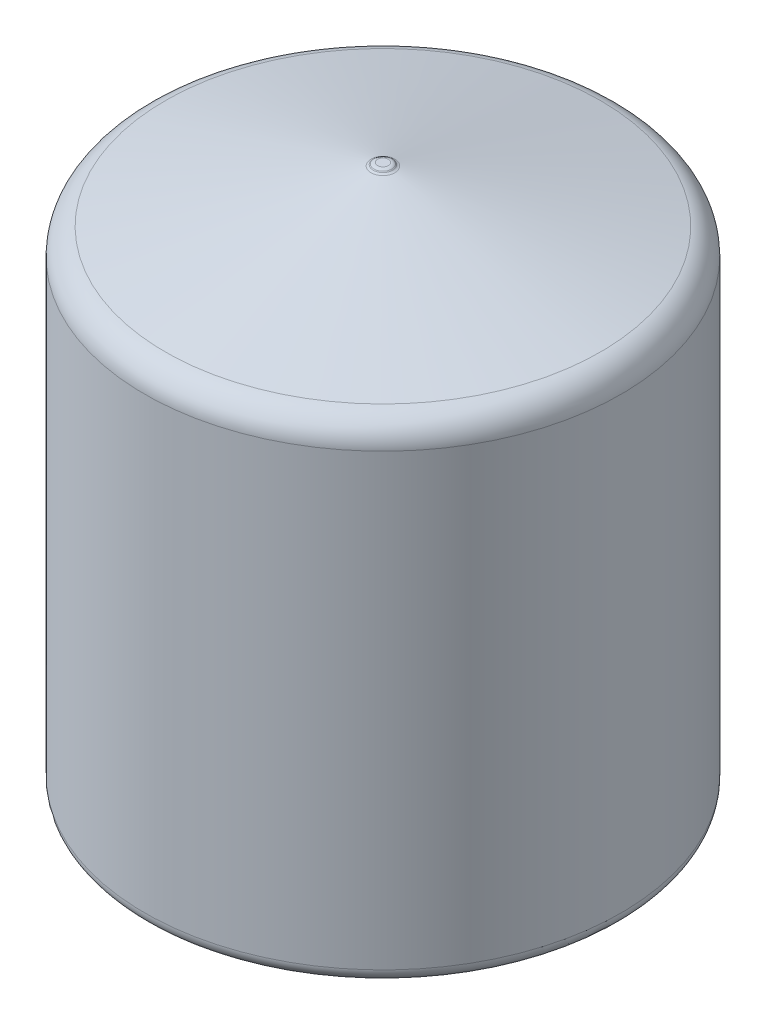
SolidWorks part; units mm, degrees
material "Zinc AC41A Alloy, As Cast"
ref_plane "Front Plane" through (0, 0, 0) normal (0, 0, 1) x (1, 0, 0)
ref_plane "Top Plane" through (0, 0, 0) normal (0, 1, 0) x (1, 0, 0)
ref_plane "Right Plane" through (0, 0, 0) normal (1, 0, 0) x (0, 0, -1)
sketch "Sketch1" plane through (0, 0, 0) normal (0, 0, 1) x (1, 0, 0)
  line L0 (7.75, 0) -> (7.75, 17)
  line L1 (7.9962, 17.9692) -> (0.4357, 19.8893)
  line L2 (8.75, 0) -> (8.75, 17)
  line L3 (0, 20) -> (0, 19.5)
  line L4 (7.75, 17) -> (0.7128, 18.7872)
  line L5 (0.3282, 19.9535) -> (0.3568, 19.9297)
  line L6 (0.2, 20) -> (0, 20)
  line L7 (7.75, 0) -> (8.75, 0)
  line L8 (0, 9.5) -> (0, 0) construction
  line L9 (0, 19.5) -> (0.7128, 18.7872)
  line L10 (0, 20) -> (-6.88, 17.1682) construction
  line L11 (0.0746, 18.9493) -> (-6.4994, 16.2434) construction
  line L12 (8.75, 17.7778) -> (0, 20) construction
  line L13 (7.75, 17) -> (0.0746, 18.9493) construction
  line L14 (8.75, 0) -> (8.75, 17.7778) construction
  arc A0 (8.75, 17) -> (7.9962, 17.9692) centre (7.75, 17) ccw
  arc A1 (0.3282, 19.9535) -> (0.2, 20) centre (0.2, 19.8) ccw
  arc A2 (0.3568, 19.9297) -> (0.4357, 19.8893) centre (0.4849, 20.0832) ccw
  dimension "D5" = 1
  dimension "D3" = 0.2
  dimension "D1" = 1
  dimension "D2" = 17.5
  dimension "D4" = 20
  dimension "D6" = 17
  dimension "D7" = 0.5
  dimension "D8" = 0.2
  dimension "D9" = 45
revolve "Revolve1" add sketch "Sketch1" angle 360 about L8 reverse direction yes
fillet "Fillet1" radius 0.5 2 edges at (0, 0, -7.75) (0, 0, -8.75)
